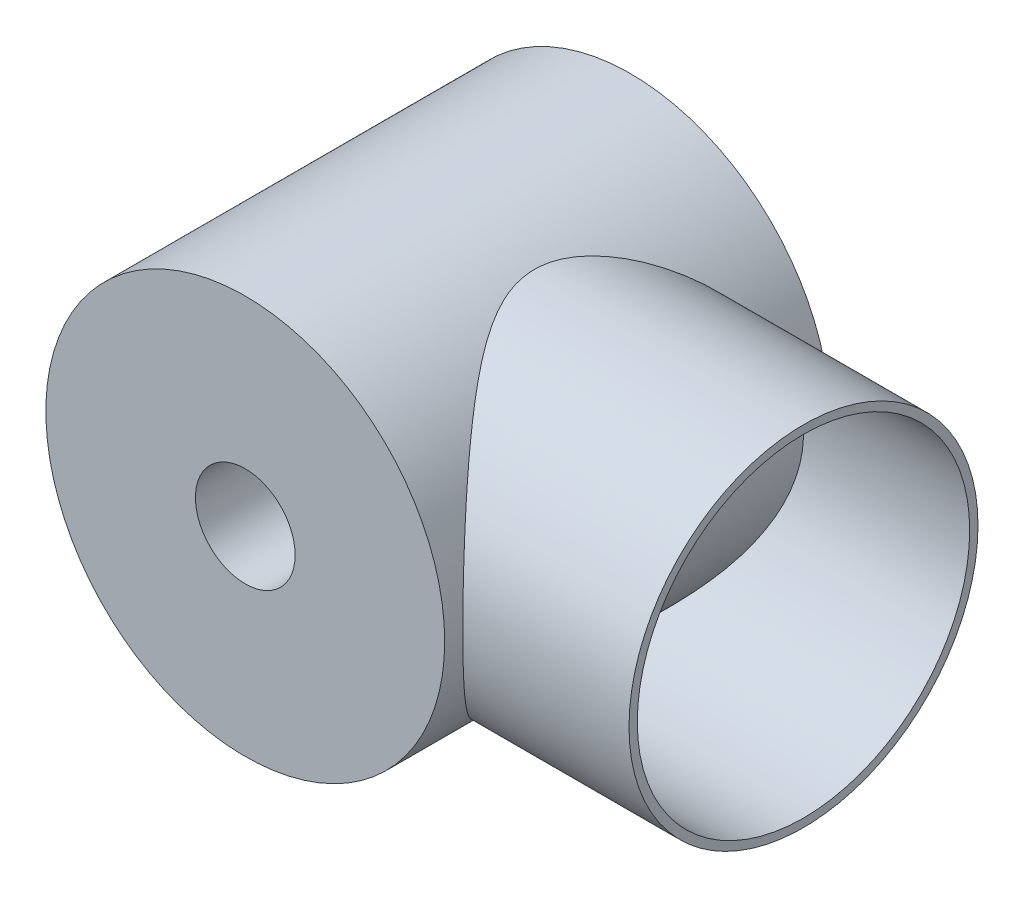
SolidWorks part; units mm, degrees
material "ABS"
ref_plane "Front Plane" through (0, 0, 0) normal (0, 0, 1) x (1, 0, 0)
ref_plane "Top Plane" through (0, 0, 0) normal (0, 1, 0) x (1, 0, 0)
ref_plane "Right Plane" through (0, 0, 0) normal (1, 0, 0) x (0, 0, -1)
sketch "Sketch1" plane through (0, 0, 0) normal (0, 0, 1) x (1, 0, 0)
  circle A0 centre (0, 0) radius 12
  dimension "D1" = 24
extrude "Boss-Extrude1" add sketch "Sketch1" along normal mid plane 23.18
sketch "Sketch3" plane through (0, 0, 0) normal (1, 0, 0) x (0, 0, -1)
  circle A0 centre (0, 0) radius 10
  dimension "D1" = 20
extrude "Extrude-Thin1" add sketch "Sketch3" along normal blind 22 thin thin type one direction wall 0.5
shell "Shell1" thickness 4.5 removed face at (12, 0, -11.59)
sketch "Sketch4" plane through (0, 0, 11.59) normal (0, 0, 1) x (1, 0, 0)
  circle A0 centre (0, 0) radius 3
  dimension "D1" = 6
extrude "Cut-Extrude1" cut sketch "Sketch4" against normal up to next
